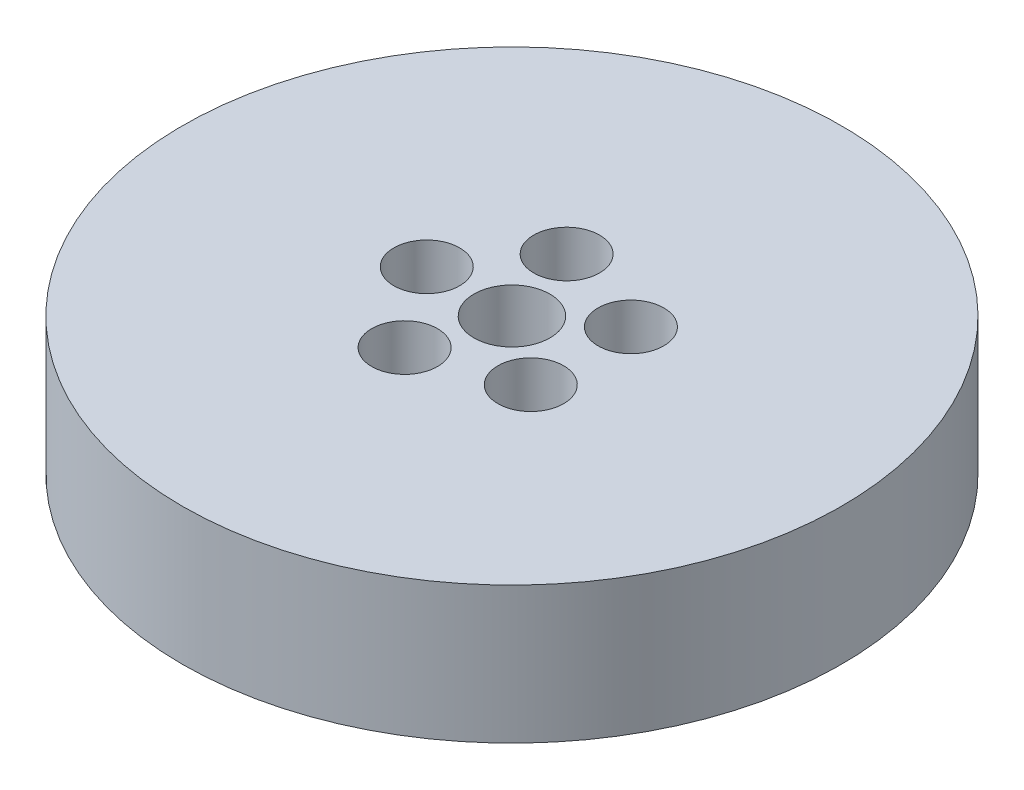
SolidWorks part; units mm, degrees
ref_plane "Front Plane" through (0, 0, 0) normal (0, 0, 1) x (1, 0, 0)
ref_plane "Top Plane" through (0, 0, 0) normal (0, 1, 0) x (1, 0, 0)
ref_plane "Right Plane" through (0, 0, 0) normal (1, 0, 0) x (0, 0, -1)
sketch "Sketch1" plane through (0, 0, 0) normal (0, 1, 0) x (1, 0, 0)
  circle A0 centre (0, 0) radius 65
  dimension "FLANGE_OD" = 130
extrude "Boss-Extrude1" add sketch "Sketch1" along normal blind 27
sketch "Sketch2" plane through (0, 0, 0) normal (0, 1, 0) x (1, 0, 0)
  circle A0 centre (0, 0) radius 7.5
  dimension "BORE_D" = 15
extrude "Cut-Extrude1" cut sketch "Sketch2" along normal through all
sketch "Sketch3" plane through (0, 27, 0) normal (0, 1, 0) x (1, 0, 0)
  circle A0 centre (0, 0) radius 16.8013 construction
  circle A1 centre (-16.8013, 0) radius 6.4872
  dimension "BOLT_D" = 12.9745
  dimension "BOLT_PCD" = 33.6026
extrude "Cut-Extrude2" cut sketch "Sketch3" against normal blind 21.0051
pattern_circular "CirPattern1" count 5 over 360 about axis through (0, 0, 0) along (0, 1, 0) of "Cut-Extrude2"
